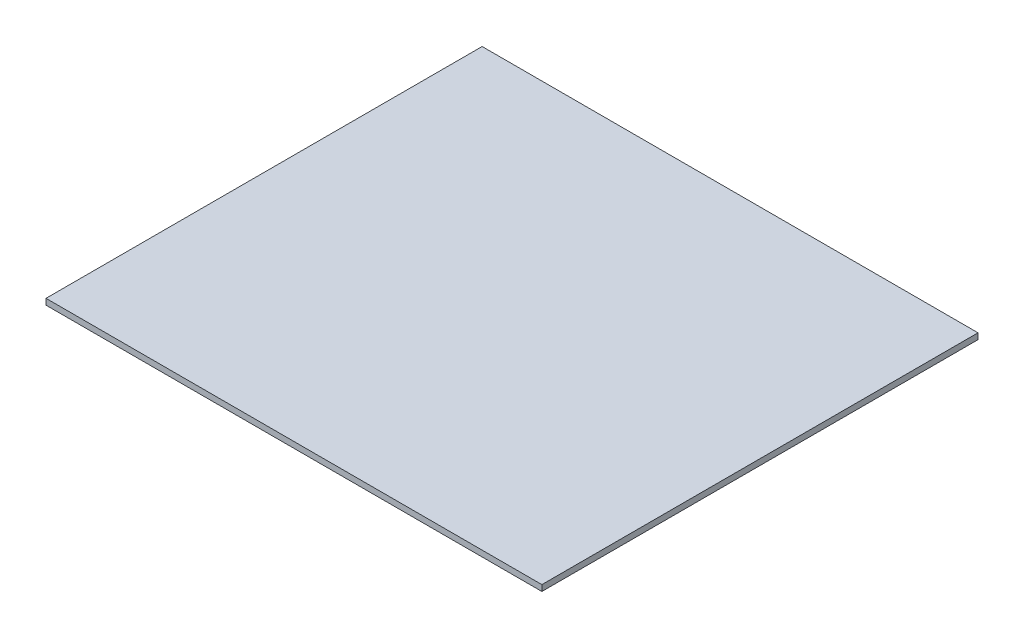
SolidWorks part; units mm, degrees
ref_plane "Front Plane" through (0, 0, 0) normal (0, 0, 1) x (1, 0, 0)
ref_plane "Top Plane" through (0, 0, 0) normal (0, 1, 0) x (1, 0, 0)
ref_plane "Right Plane" through (0, 0, 0) normal (1, 0, 0) x (0, 0, -1)
sketch "Sketch1" plane through (0, 0, 0) normal (0, 1, 0) x (1, 0, 0)
  line L1 (-210.82, 99.0051) -> (0, 99.0051)
  line L2 (-210.82, 99.0051) -> (-210.82, -86.4149)
  line L3 (-210.82, -86.4149) -> (0, -86.4149)
  line L4 (0, 99.0051) -> (0, -86.4149)
  dimension "D1" = 210.82
  dimension "D2" = 185.42
extrude "Boss-Extrude1" add sketch "Sketch1" along normal blind 2.54
